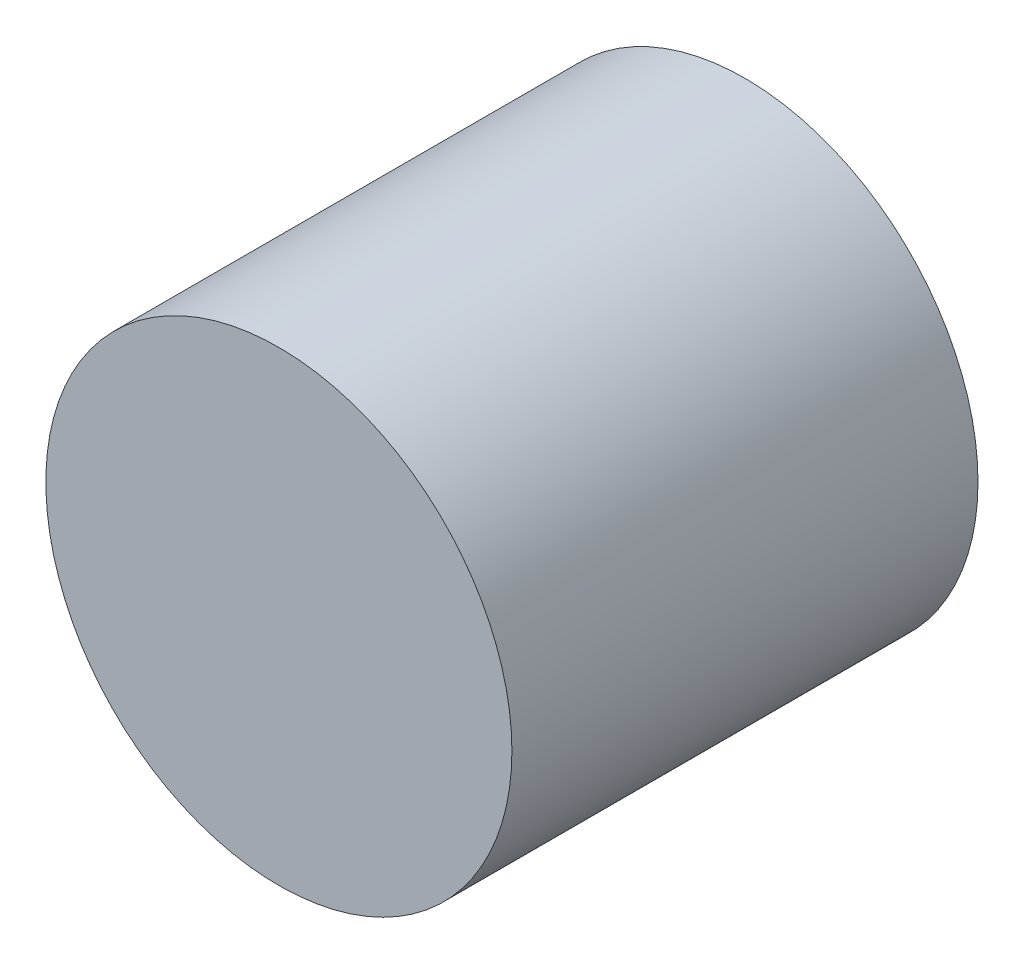
SolidWorks part; units mm, degrees
ref_plane "Front Plane" through (0, 0, 0) normal (0, 0, 1) x (1, 0, 0)
ref_plane "Top Plane" through (0, 0, 0) normal (0, 1, 0) x (1, 0, 0)
ref_plane "Right Plane" through (0, 0, 0) normal (1, 0, 0) x (0, 0, -1)
sketch "Sketch2" plane through (0, 0, 0) normal (0, 0, 1) x (1, 0, 0)
  circle A0 centre (0, 0) radius 4.7625 construction
  circle A1 centre (0, 0) radius 7.9375
  dimension "D1" = 15.875
  dimension "D2" = 9.525
extrude "Boss-Extrude1" add sketch "Sketch2" along normal blind 15.875
